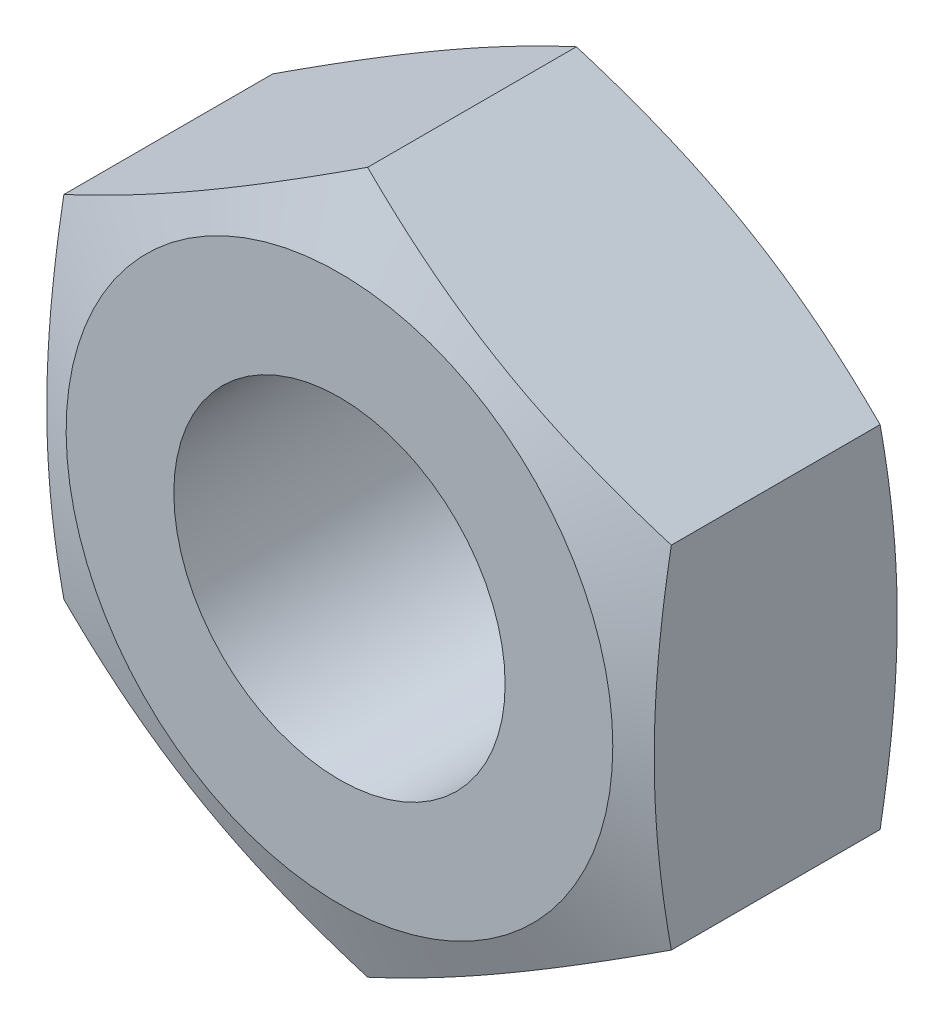
SolidWorks part; units mm, degrees
ref_plane "前视基准面" through (0, 0, 0) normal (0, 0, 1) x (1, 0, 0)
ref_plane "上视基准面" through (0, 0, 0) normal (0, 1, 0) x (1, 0, 0)
ref_plane "右视基准面" through (0, 0, 0) normal (1, 0, 0) x (0, 0, -1)
sketch "草图1" plane through (0, 0, 0) normal (0, 0, 1) x (1, 0, 0)
  line L1 (0, 3.1754) -> (-2.75, 1.5877)
  line L2 (-2.75, 1.5877) -> (-2.75, -1.5877)
  line L3 (-2.75, -1.5877) -> (0, -3.1754)
  line L4 (0, -3.1754) -> (2.75, -1.5877)
  line L5 (2.75, -1.5877) -> (2.75, 1.5877)
  line L6 (2.75, 1.5877) -> (0, 3.1754)
  circle A0 centre (0, 0) radius 2.75 construction
  dimension "s" = 5.5
extrude "凸台-拉伸1" add sketch "草图1" along normal blind 2.4
sketch "草图4" plane through (0, 0, 0) normal (1, 0, 0) x (0, 0, -1)
  line L0 (-2.4, -2.475) -> (-2.1451, -3.1754)
  line L1 (-2.4, -1.5877) -> (-2.4, -3.1754) construction
  line L2 (-2.4, -3.1754) -> (0, -3.1754) construction
  line L3 (-2.1451, -3.1754) -> (-2.4, -3.1754)
  line L4 (-2.4, -3.1754) -> (-2.4, -2.475)
  line L5 (-2.4, 0) -> (0, 0) construction
  line L6 (-2.4, 1.5877) -> (-2.4, -1.5877) construction
  line L7 (0, 1.5877) -> (0, -1.5877) construction
  dimension "D1" = 20
  dimension "D2" = 2.475
revolve "切除-旋转1" cut sketch "草图4" angle 360 about L5
ref_plane "基准面1" through (0, 0, 1.2) normal (0, 0, 1) x (1, 0, 0)
mirror "镜向1" about plane through (0, 0, 1.2) normal (0, 0, 1) of "切除-旋转1"
sketch "草图5" plane through (0, 0, 2.4) normal (0, 0, 1) x (1, 0, 0)
  circle A0 centre (0, 0) radius 1.5
  dimension "D1" = 3
extrude "切除-拉伸1" cut sketch "草图5" against normal through all
ref_axis "基准轴1" through (0, 0, 0) along (0, 0, 1)
ref_plane "基准面2" through (0, 0, 0) normal (0, 0, -1) x (-1, 0, 0)
ref_plane "基准面3" through (0, 0, 2.4) normal (0, 0, 1) x (1, 0, 0)
equation "\"D2@草图4\"= \"s@草图1\" * 0.45"
